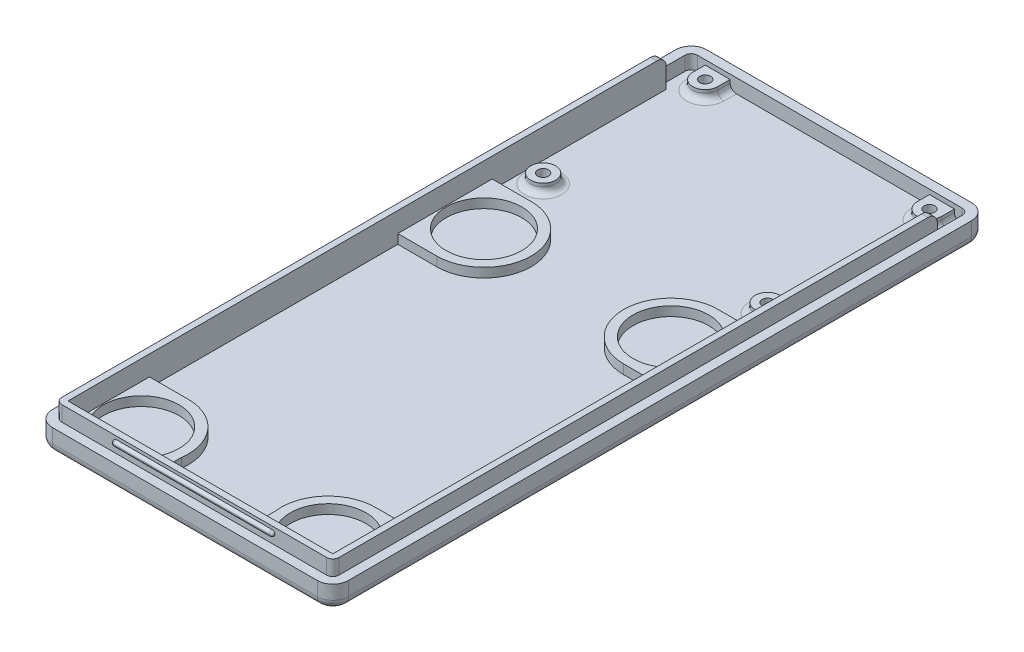
SolidWorks part; units mm, degrees
material "ABS"
ref_plane "Front Plane" through (0, 0, 0) normal (0, 0, 1) x (1, 0, 0)
ref_plane "Top Plane" through (0, 0, 0) normal (0, 1, 0) x (1, 0, 0)
ref_plane "Right Plane" through (0, 0, 0) normal (1, 0, 0) x (0, 0, -1)
sketch "Sketch1" plane through (0, 0, 0) normal (0, 1, 0) x (1, 0, 0)
  line L1 (-42.5, -105) -> (42.5, -105)
  line L2 (-47.5, -100) -> (-47.5, 100)
  line L3 (-42.5, 105) -> (42.5, 105)
  line L4 (47.5, -100) -> (47.5, 100)
  line L5 (-47.5, -105) -> (47.5, 105) construction
  line L6 (-47.5, 105) -> (47.5, -105) construction
  arc A0 (42.5, -105) -> (47.5, -100) centre (42.5, -100) ccw
  arc A1 (-42.5, -105) -> (-47.5, -100) centre (-42.5, -100) cw
  arc A2 (42.5, 105) -> (47.5, 100) centre (42.5, 100) cw
  arc A3 (-47.5, 100) -> (-42.5, 105) centre (-42.5, 100) cw
  point P0 (0, 0)
  dimension "D3" = 5
  dimension "D1" = 95
  dimension "D2" = 210
extrude "Boss-Extrude1" add sketch "Sketch1" along normal blind 3
sketch "Sketch2" plane through (0, 3, 0) normal (0, 1, 0) x (1, 0, 0)
  line L1 (42.5, 105) -> (-42.5, 105) construction
  line L2 (47.5, -100) -> (47.5, 100) construction
  line L3 (-47.5, 100) -> (-47.5, -100) construction
  line L4 (-42.5, -105) -> (42.5, -105) construction
  line L5 (42.5, 105) -> (-42.5, 105)
  line L6 (47.5, -100) -> (47.5, 100)
  line L7 (-47.5, 100) -> (-47.5, -100)
  line L8 (-42.5, -105) -> (42.5, -105)
  line L9 (42.5, 102) -> (-42.5, 102)
  line L10 (-44.5, 100) -> (-44.5, -100)
  line L11 (-42.5, -102) -> (42.5, -102)
  line L12 (44.5, -100) -> (44.5, 100)
  arc A0 (-42.5, 105) -> (-47.5, 100) centre (-42.5, 100) ccw construction
  arc A1 (47.5, 100) -> (42.5, 105) centre (42.5, 100) ccw construction
  arc A2 (42.5, -105) -> (47.5, -100) centre (42.5, -100) ccw construction
  arc A3 (-47.5, -100) -> (-42.5, -105) centre (-42.5, -100) ccw construction
  arc A4 (-42.5, 105) -> (-47.5, 100) centre (-42.5, 100) ccw
  arc A5 (47.5, 100) -> (42.5, 105) centre (42.5, 100) ccw
  arc A6 (42.5, -105) -> (47.5, -100) centre (42.5, -100) ccw
  arc A7 (-47.5, -100) -> (-42.5, -105) centre (-42.5, -100) ccw
  arc A8 (-42.5, 102) -> (-44.5, 100) centre (-42.5, 100) ccw
  arc A9 (-44.5, -100) -> (-42.5, -102) centre (-42.5, -100) ccw
  arc A10 (42.5, -102) -> (44.5, -100) centre (42.5, -100) ccw
  arc A11 (44.5, 100) -> (42.5, 102) centre (42.5, 100) ccw
  dimension "D1" = 3
extrude "Boss-Extrude2" add sketch "Sketch2" along normal blind 4.5
sketch "Sketch3" plane through (0, 3, 0) normal (0, 1, 0) x (1, 0, 0)
  line L0 (0, 105) -> (0, -102) construction
  line L1 (42.5, 105) -> (-42.5, 105) construction
  line L2 (42.5, 102) -> (-42.5, 102) construction
  line L3 (-42.5, -102) -> (42.5, -102) construction
  line L25 (-15, -91.1266) -> (-15, -102)
  line L44 (-40, 98) -> (-40, 102)
  line L45 (-40, 102) -> (-32, 102)
  line L46 (42.5, 102) -> (-42.5, 102) construction
  line L47 (-32, 102) -> (-32, 98)
  line L48 (32, 102) -> (32, 98)
  line L49 (40, 102) -> (32, 102)
  line L50 (40, 98) -> (40, 102)
  line L51 (-30, -73.85) -> (-44.5, -73.85)
  line L52 (-44.5, 100) -> (-44.5, -100) construction
  line L53 (-44.5, -73.85) -> (-44.5, -102)
  line L55 (-15, -102) -> (-44.5, -102)
  line L56 (-30, 36.15) -> (-44.5, 36.15)
  line L57 (-44.5, 36.15) -> (-44.5, 5.85)
  line L58 (-44.5, 5.85) -> (-30, 5.85)
  line L59 (44.5, 5.85) -> (30, 5.85)
  line L60 (44.5, 36.15) -> (44.5, 5.85)
  line L61 (30, 36.15) -> (44.5, 36.15)
  line L62 (15, -102) -> (44.5, -102)
  line L63 (44.5, -73.85) -> (44.5, -102)
  line L64 (30, -73.85) -> (44.5, -73.85)
  line L65 (15, -91.1266) -> (15, -102)
  circle A0 centre (-36, 98) radius 1.4
  arc A1 (-40, 98) -> (-32, 98) centre (-36, 98) ccw
  circle A2 centre (-36, 46) radius 1.4
  circle A3 centre (-36, 46) radius 4
  circle A4 centre (36, 46) radius 4
  circle A5 centre (36, 46) radius 1.4
  arc A24 (-44.5, -100) -> (-42.5, -102) centre (-42.5, -100) ccw construction
  arc A34 (40, 98) -> (32, 98) centre (36, 98) cw
  circle A35 centre (36, 98) radius 1.4
  circle A36 centre (-30, -89) radius 12.15
  circle A37 centre (-30, 21) radius 12.15
  arc A38 (-15, -91.1266) -> (-30, -73.85) centre (-30, -89) ccw
  arc A39 (-30, 5.85) -> (-30, 36.15) centre (-30, 21) ccw
  circle A40 centre (-30, -89) radius 15.15 construction
  circle A41 centre (-30, 21) radius 15.15 construction
  arc A42 (30, 5.85) -> (30, 36.15) centre (30, 21) cw
  arc A43 (15, -91.1266) -> (30, -73.85) centre (30, -89) cw
  circle A44 centre (30, 21) radius 12.15
  circle A45 centre (30, -89) radius 12.15
  point P29 (0, 0)
  point P43 (0, 0)
  point P61 (0, 0)
  point P62 (0, 0)
  dimension "D4" = 2.8
  dimension "D5" = 24.3
  dimension "D6" = 8
  dimension "D7" = 8
  dimension "D11" = 3
  dimension "D12" = 29.5
  dimension "D15" = 8
  dimension "D8" = 110
  dimension "D14" = 2.8
  dimension "D2" = 24.3
  dimension "D16" = 14.5
  dimension "D1" = 36
  dimension "D3" = 4
  dimension "D9" = 30
  dimension "D10" = 13
  dimension "D13" = 52
extrude "Boss-Extrude3" add sketch "Sketch3" along normal blind 3
sketch "Sketch5" plane through (0, 7.5, 0) normal (0, 1, 0) x (1, 0, 0)
  line L25 (-42.5, -102) -> (42.5, -102) construction
  line L26 (44.5, -100) -> (44.5, 100) construction
  line L27 (-44.5, 100) -> (-44.5, -100) construction
  line L28 (-42.5, -102) -> (42.5, -102)
  line L30 (44.5, -100) -> (44.5, 92)
  line L31 (-44.5, 92) -> (-44.5, -100)
  line L32 (-42.5, 92) -> (-42.5, -100)
  line L33 (-42.5, -100) -> (42.5, -100)
  line L39 (42.5, -100) -> (42.5, 92)
  line L40 (-44.5, 92) -> (-42.5, 92)
  line L45 (-44.5, 100) -> (-44.5, -100) construction
  line L46 (-42.5, 100) -> (-42.5, -100) construction
  line L47 (42.5, 92) -> (44.5, 92)
  line L48 (42.5, -100) -> (42.5, 100) construction
  line L49 (44.5, -100) -> (44.5, 100) construction
  line L50 (42.5, 102) -> (-42.5, 102) construction
  arc A16 (-44.5, -100) -> (-42.5, -102) centre (-42.5, -100) ccw construction
  arc A17 (42.5, -102) -> (44.5, -100) centre (42.5, -100) ccw construction
  arc A18 (-44.5, -100) -> (-42.5, -102) centre (-42.5, -100) ccw
  arc A19 (42.5, -102) -> (44.5, -100) centre (42.5, -100) ccw
  arc A20 (-42.5, -100) -> (-42.5, -100) centre (-42.5, -100) ccw
  arc A21 (42.5, -100) -> (42.5, -100) centre (42.5, -100) ccw
  point P18 (0, 0)
  point P22 (0, 0)
  point P23 (0, 0)
  dimension "D2" = 10
  dimension "D1" = 2
sketch "Sketch6" plane through (0, 6, 0) normal (0, 1, 0) x (1, 0, 0)
  circle A0 centre (-36, 98) radius 1.75
  circle A1 centre (36, 98) radius 1.75
  circle A2 centre (36, 98) radius 1.4 construction
  circle A3 centre (-36, 46) radius 1.75
  circle A4 centre (36, 46) radius 1.75
  dimension "D1" = 3.5
  dimension "D2" = 3.5
  dimension "D3" = 3.5
  dimension "D4" = 3.5
extrude "Cut-Extrude3" cut sketch "Sketch6" against normal up to next
extrude "Boss-Extrude5" add sketch "Sketch5" along normal blind 4.9 and the other way up to next
fillet "Fillet3" radius 3 2 edges at (-43.5, 12.4, -92) (43.5, 12.4, -92)
sketch "Sketch8" plane through (0, 0, 102) normal (0, 0, 1) x (1, 0, 0)
  line L0 (-25, 10.5) -> (25, 10.5) construction
  line L1 (-25, 11.4) -> (25, 11.4)
  line L2 (-25, 9.6) -> (25, 9.6)
  line L4 (-42.5, 7.5) -> (42.5, 7.5) construction
  arc A0 (-25, 11.4) -> (-25, 9.6) centre (-25, 10.5) ccw
  arc A1 (25, 9.6) -> (25, 11.4) centre (25, 10.5) ccw
  point P2 (0, 10.5)
  dimension "D1" = 50
  dimension "D2" = 3
  dimension "D3" = 1.8
extrude "Boss-Extrude6" add sketch "Sketch8" along normal blind 0.9
fillet "Fillet4" radius 0.9 4 edges at (25.9, 10.5, 102.9) (0, 9.6, 102.9) (-25.9, 10.5, 102.9) (0, 11.4, 102.9)
chamfer "Chamfer4" distance 1.5 angle 45 4 edges at (-36, 0, -96.25) (36, 0, -96.25) (-36, 0, -44.25) (36, 0, -44.25)
fillet "Fillet6" radius 2 8 edges at (-40, 3, -100) (-32, 3, -100) (32, 3, -100) (40, 3, -100) (-36, 3, -94) (36, 3, -94) (36, 3, -50) (-36, 3, -42)
fillet "Fillet7" radius 3 8 edges at (-46.0355, 0, -103.5355) (0, 0, -105) (46.0355, 0, -103.5355) (47.5, 0, 0) (46.0355, 0, 103.5355) (0, 0, 105) (-46.0355, 0, 103.5355) (-47.5, 0, 0)
